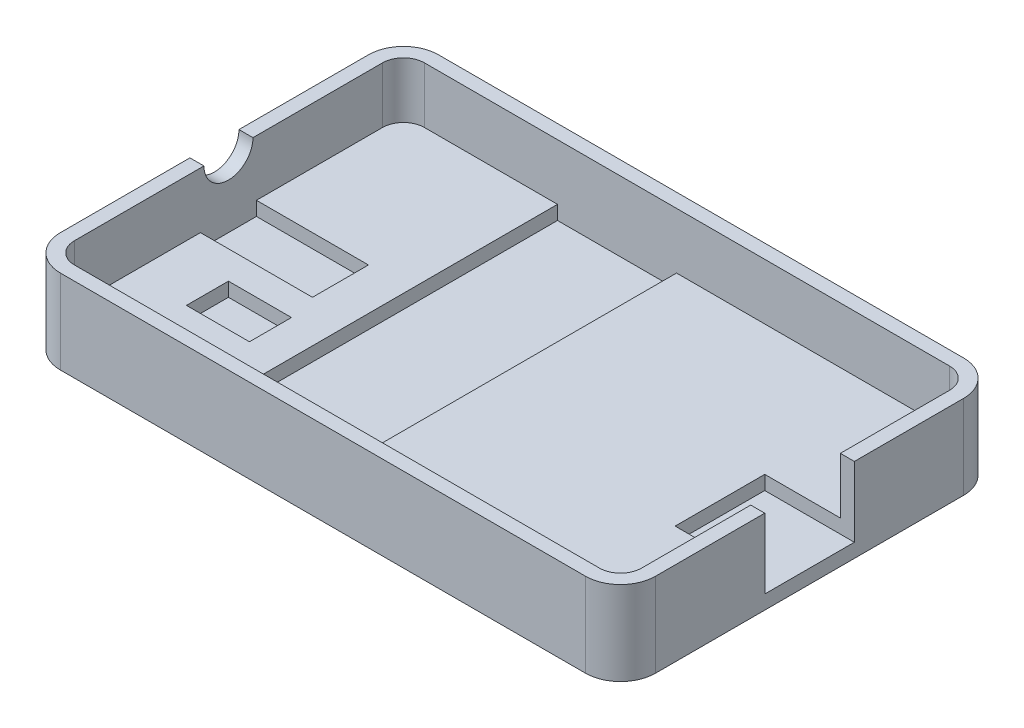
SolidWorks part; units mm, degrees
ref_plane "Front Plane" through (0, 0, 0) normal (0, 0, 1) x (1, 0, 0)
ref_plane "Top Plane" through (0, 0, 0) normal (0, 1, 0) x (1, 0, 0)
ref_plane "Right Plane" through (0, 0, 0) normal (1, 0, 0) x (0, 0, -1)
sketch "Sketch1" plane through (0, 0, 0) normal (0, 1, 0) x (1, 0, 0)
  line L1 (-21.25, 13.5) -> (21.25, 13.5)
  line L2 (-21.25, 13.5) -> (-21.25, -13.5)
  line L3 (-21.25, -13.5) -> (21.25, -13.5)
  line L4 (21.25, 13.5) -> (21.25, -13.5)
  line L5 (-21.25, 13.5) -> (21.25, -13.5) construction
  line L6 (-21.25, -13.5) -> (21.25, 13.5) construction
  point P0 (0, 0)
  dimension "D1" = 27
  dimension "D2" = 42.5
extrude "Boss-Extrude1" add sketch "Sketch1" along normal blind 6
sketch "Sketch2" plane through (0, 6, 0) normal (0, 1, 0) x (1, 0, 0)
  line L0 (-21.25, -13.5) -> (21.25, -13.5) construction
  line L1 (-20.25, 12.5) -> (20.25, 12.5)
  line L2 (-20.25, 12.5) -> (-20.25, -12.5)
  line L3 (-20.25, -12.5) -> (20.25, -12.5)
  line L4 (20.25, 12.5) -> (20.25, -12.5)
  line L5 (-20.25, 12.5) -> (20.25, -12.5) construction
  line L6 (-20.25, -12.5) -> (20.25, 12.5) construction
  line L7 (-21.25, 13.5) -> (-21.25, -13.5) construction
  point P0 (0, 0)
  dimension "D1" = 1
  dimension "D2" = 1
extrude "Cut-Extrude1" cut sketch "Sketch2" against normal blind 4
sketch "Sketch3" plane through (0, 6, 0) normal (0, 1, 0) x (1, 0, 0)
  line L0 (21.25, 0) -> (0, 0) construction
  line L1 (21.25, -13.5) -> (21.25, 13.5) construction
  line L3 (14.85, 3.2) -> (21.25, 3.2)
  line L4 (14.85, 3.2) -> (14.85, -3.2)
  line L5 (14.85, -3.2) -> (21.25, -3.2)
  line L6 (21.25, 3.2) -> (21.25, -3.2)
  line L7 (14.85, 3.2) -> (21.25, -3.2) construction
  line L8 (14.85, -3.2) -> (21.25, 3.2) construction
  point P5 (18.05, 0)
  dimension "D1" = 6.4
  dimension "D2" = 6.4
extrude "Cut-Extrude2" cut sketch "Sketch3" against normal blind 5
sketch "Sketch4" plane through (-21.25, 0, 0) normal (-1, 0, 0) x (0, 0, 1)
  line L0 (-13.5, 6) -> (13.5, 6) construction
  circle A1 centre (0, 6) radius 1.75
  dimension "D1" = 3.5
extrude "Cut-Extrude3" cut sketch "Sketch4" against normal up to next contours A1
sketch "Sketch5" plane through (0, 2, 0) normal (0, 1, 0) x (1, 0, 0)
  line L0 (20.25, 12.5) -> (-20.25, 12.5) construction
  line L1 (-9.25, 12.5) -> (-0.75, 12.5)
  line L2 (-9.25, 12.5) -> (-9.25, -12.5)
  line L3 (-9.25, -12.5) -> (-0.75, -12.5)
  line L4 (-0.75, 12.5) -> (-0.75, -12.5)
  line L5 (-20.25, -12.5) -> (20.25, -12.5) construction
  line L6 (-20.25, 12.5) -> (-20.25, 1.75) construction
  dimension "D1" = 11
  dimension "D2" = 8.5
extrude "Cut-Extrude4" cut sketch "Sketch5" against normal blind 1
sketch "Sketch6" plane through (0, 2, 0) normal (0, 1, 0) x (1, 0, 0)
  line L0 (-9.25, 0) -> (-20.25, 0)
  line L1 (-9.25, 12.5) -> (-9.25, -12.5) construction
  line L2 (-20.25, 12.5) -> (-20.25, -12.5) construction
  line L4 (-12.25, 2) -> (-20.25, 2)
  line L5 (-12.25, 2) -> (-12.25, -2)
  line L6 (-12.25, -2) -> (-20.25, -2)
  line L7 (-20.25, 2) -> (-20.25, -2)
  line L8 (-12.25, 2) -> (-20.25, -2) construction
  line L9 (-12.25, -2) -> (-20.25, 2) construction
  point P6 (-16.25, 0)
  dimension "D1" = 4
  dimension "D2" = 8
extrude "Cut-Extrude5" cut sketch "Sketch6" against normal blind 1 contours L5 L6 L7 L4
sketch "Sketch7" plane through (0, 2, 0) normal (0, 1, 0) x (1, 0, 0)
  line L0 (-20.25, -2) -> (-20.25, -12.5) construction
  line L1 (-16.25, -4) -> (-11.75, -4)
  line L2 (-16.25, -4) -> (-16.25, -7)
  line L3 (-16.25, -7) -> (-11.75, -7)
  line L4 (-11.75, -4) -> (-11.75, -7)
  line L5 (-16.25, -4) -> (-11.75, -7) construction
  line L6 (-16.25, -7) -> (-11.75, -4) construction
  line L7 (-9.25, 12.5) -> (-20.25, 12.5) construction
  point P0 (-14, -5.5)
  dimension "D1" = 4.5
  dimension "D2" = 3
  dimension "D3" = 4
  dimension "D4" = 16.5
extrude "Cut-Extrude6" cut sketch "Sketch7" against normal blind 1
fillet "Fillet1" radius 1.5 4 edges at (20.25, 4, 12.5) (-20.25, 4, 12.5) (20.25, 4, -12.5) (-20.25, 4, -12.5)
fillet "Fillet2" radius 2.5 4 edges at (-21.25, 3, -13.5) (21.25, 3, -13.5) (21.25, 3, 13.5) (-21.25, 3, 13.5)
